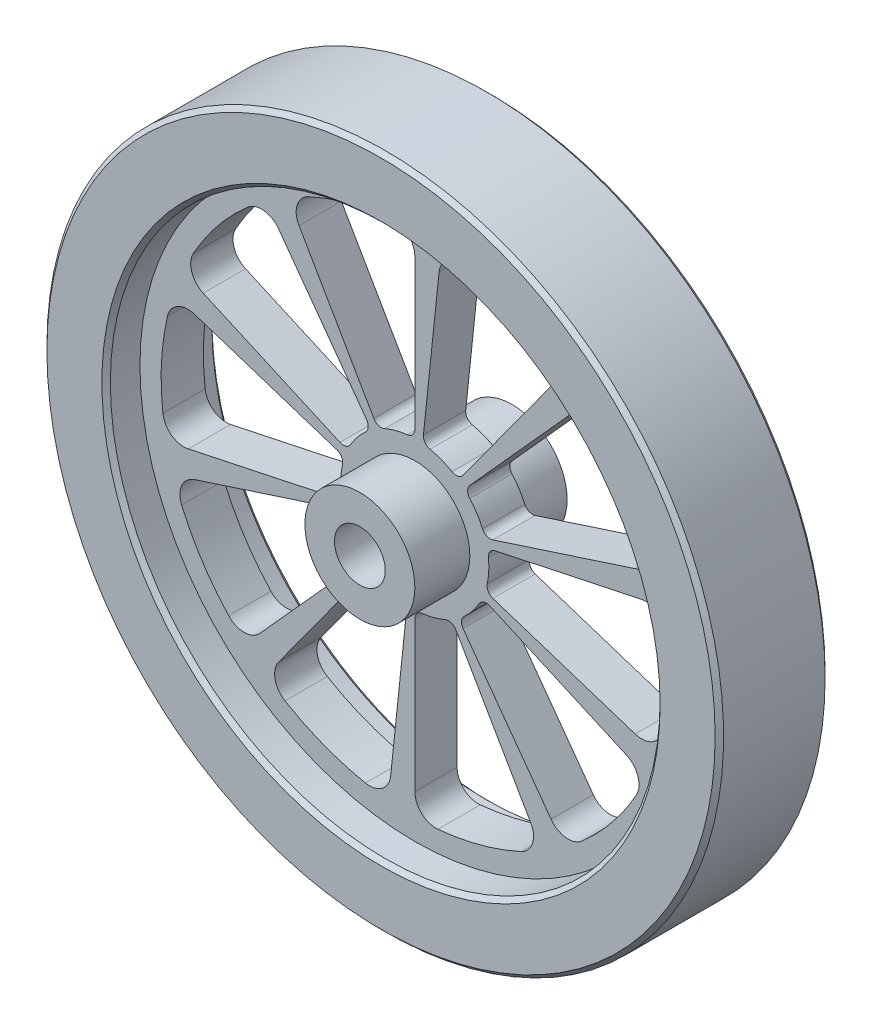
SolidWorks part; units mm, degrees
ref_plane "Front Plane" through (0, 0, 0) normal (0, 0, 1) x (1, 0, 0)
ref_plane "Top Plane" through (0, 0, 0) normal (0, 1, 0) x (1, 0, 0)
ref_plane "Right Plane" through (0, 0, 0) normal (1, 0, 0) x (0, 0, -1)
sketch "Sketch3" plane through (0, 0, 0) normal (0, 0, 1) x (1, 0, 0)
  circle A0 centre (0, 0) radius 80
  circle A1 centre (0, 0) radius 6
  dimension "D1" = 12
  dimension "D2" = 160
extrude "Boss-Extrude2" add sketch "Sketch3" along normal mid plane 26
sketch "Sketch4" plane through (0, 0, 13) normal (0, 0, 1) x (1, 0, 0)
  circle A0 centre (0, 0) radius 65
  dimension "D1" = 130
extrude "Cut-Extrude3" cut sketch "Sketch4" against normal blind 8
mirror "Mirror2" about plane through (0, 0, 0) normal (0, 0, 1) of "Cut-Extrude3"
sketch "Sketch5" plane through (0, 0, 0) normal (0, 0, 1) x (1, 0, 0)
  circle A0 centre (0, 0) radius 6 construction
  circle A1 centre (0, 0) radius 6
  circle A2 centre (0, 0) radius 13
  dimension "D1" = 26
extrude "Boss-Extrude3" add sketch "Sketch5" along normal mid plane 36
chamfer "Chamfer1" distance 1 angle 45 4 edges at (80, 0, -13) (65, 0, -13) (80, 0, 13) (65, 0, 13)
sketch "Sketch6" plane through (0, 0, 5) normal (0, 0, 1) x (1, 0, 0)
  line L0 (0, 17.5) -> (0, 60) construction
  line L1 (0, 0) -> (-30, 51.9615) construction
  line L2 (-27.3861, 47.4342) -> (-9.6986, 16.7984)
  line L3 (0, 54.7723) -> (0, 19.3972)
  arc A0 (-5.4545, 59.7516) -> (-25.152, 54.4736) centre (0, 0) ccw
  arc A1 (-1.7949, 17.4077) -> (-7.1495, 15.973) centre (0, 0) ccw
  arc A2 (-27.3861, 47.4342) -> (-25.152, 54.4736) centre (-23.056, 49.9342) cw
  arc A3 (0, 54.7723) -> (-5.4545, 59.7516) centre (-5, 54.7723) ccw
  arc A4 (-7.1495, 15.973) -> (-9.6986, 16.7984) centre (-7.9665, 17.7984) cw
  arc A5 (0, 19.3972) -> (-1.7949, 17.4077) centre (-2, 19.3972) cw
  point P14 (-8.75, 15.1554)
  dimension "D1" = 35
  dimension "D2" = 120
  dimension "D4" = 5
  dimension "D5" = 2
  dimension "D3" = 30
extrude "Cut-Extrude4" cut sketch "Sketch6" against normal through all
pattern_circular "CirPattern1" count 10 over 360 about axis through (0, 0, 5) along (0, 0, 1) of "Cut-Extrude4"
